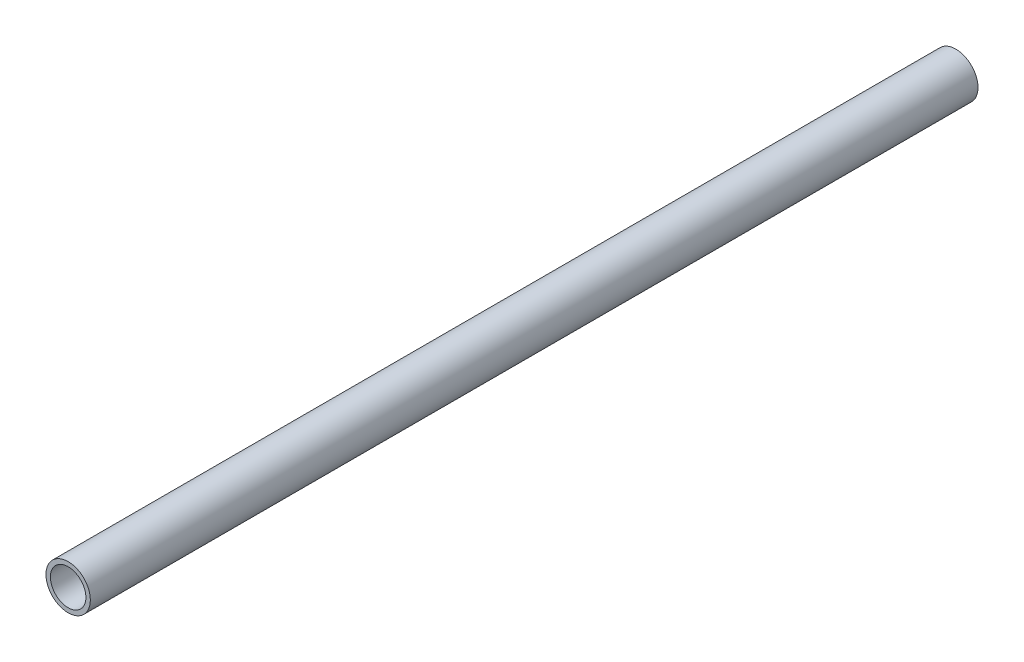
SolidWorks part; units mm, degrees
ref_plane "Front Plane" through (0, 0, 0) normal (0, 0, 1) x (1, 0, 0)
ref_plane "Top Plane" through (0, 0, 0) normal (0, 1, 0) x (1, 0, 0)
ref_plane "Right Plane" through (0, 0, 0) normal (1, 0, 0) x (0, 0, -1)
sketch "Sketch2" plane through (0, 0, 0) normal (0, 0, 1) x (1, 0, 0)
  circle A0 centre (0, 0) radius 12.5
  dimension "D1" = 25
extrude "Extrude-Thin1" add sketch "Sketch2" along normal mid plane 500 thin thin type one direction reverse wall 2.5
